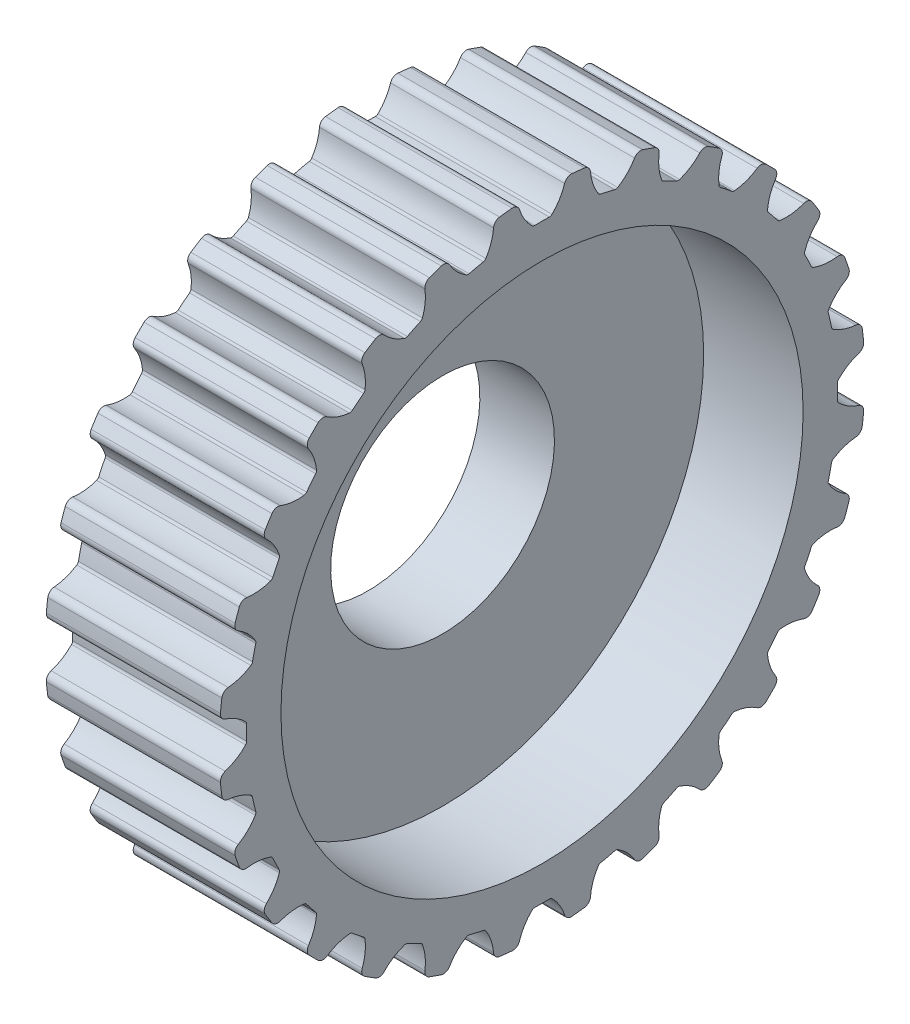
SolidWorks part; units mm, degrees
material "POM 乙缩醛共聚物"
ref_plane "前视基准面" through (0, 0, 0) normal (0, 0, 1) x (1, 0, 0)
ref_plane "上视基准面" through (0, 0, 0) normal (0, 1, 0) x (1, 0, 0)
ref_plane "右视基准面" through (0, 0, 0) normal (1, 0, 0) x (0, 0, -1)
ref_plane "基准面1" through (0, 0, 0) normal (0, 0, 1) x (1, 0, 0)
sketch "草图1" plane through (0, 0, 0) normal (0, 0, 1) x (1, 0, 0)
  line L0 (0, 0) -> (0, 10)
  line L1 (0, 10) -> (1, 10)
  line L2 (1, 10) -> (1, 12.8583)
  line L3 (1, 12.8583) -> (0.4955, 14.7412)
  line L4 (0.4955, 14.7412) -> (1.4614, 15)
  line L5 (1.4614, 15) -> (2, 12.99)
  line L6 (2, 12.99) -> (9, 12.99)
  line L7 (9, 12.99) -> (9.5386, 15)
  line L8 (9.5386, 15) -> (10.5045, 14.7412)
  line L9 (10.5045, 14.7412) -> (10, 12.8583)
  line L10 (10, 12.8583) -> (10, 10)
  line L11 (10, 10) -> (11, 10)
  line L12 (11, 10) -> (11, 0)
  line L13 (11, 0) -> (0, 0)
  line L14 (11, 0) -> (0, 0) construction
revolve "旋转1" add sketch "草图1" angle 360 about L14 reverse direction yes
ref_plane "基准面2" through (0, 0, 0) normal (0, 0, 1) x (1, 0, 0)
hole_wizard "孔1" positions "草图3" profile "草图2" legacy
sketch "草图3" plane through (11, 0, 0) normal (1, 0, 0) x (0, 0, -1)
  point P0 (0, 0)
sketch "草图2" plane through (11, 0, 0) normal (0, 1, 0) x (0, 0, -1)
  line L0 (0, 0) -> (0, 11)
  line L1 (0, 11) -> (4.5, 11)
  line L2 (4.5, 11) -> (4.5, 0)
  line L3 (4.5, 0) -> (0, 0)
  line L4 (0, 110) -> (0, -10) construction
  dimension "直径" = 9
  dimension "深度" = 11
ref_plane "基准面3" through (2, 0, 0) normal (1, 0, 0) x (0, 0, -1)
sketch "草图4" plane through (2, 0, 0) normal (1, 0, 0) x (0, 0, -1)
  circle A0 centre (0, 0) radius 17.99
  arc A1 (-12.9343, 1.2013) -> (-12.7398, 0.9084) centre (-12.6555, 1.1754) ccw
  arc A2 (-12.7398, 0.9084) -> (-11.9188, 0.4022) centre (-13.3344, -0.975) cw
  arc A3 (-11.9188, 0.4022) -> (-11.8764, 0.2939) centre (-12.0263, 0.2976) cw
  arc A4 (-11.8764, 0.2939) -> (-11.8764, -0.2939) centre (0, 0) ccw
  arc A5 (-11.8764, -0.2939) -> (-11.9188, -0.4022) centre (-12.0263, -0.2976) cw
  arc A6 (-11.9188, -0.4022) -> (-12.7398, -0.9084) centre (-13.3344, 0.975) cw
  arc A7 (-12.7398, -0.9084) -> (-12.9343, -1.2013) centre (-12.6555, -1.1754) ccw
  arc A8 (-12.9343, -1.2013) -> (-12.8774, -1.707) centre (0, 0) ccw
  arc A9 (-12.8774, -1.707) -> (-12.6225, -1.9493) centre (-12.5998, -1.6702) ccw
  arc A10 (-12.6225, -1.9493) -> (-11.7095, -2.2601) centre (-12.7831, -3.9177) cw
  arc A11 (-11.7095, -2.2601) -> (-11.644, -2.3562) centre (-11.791, -2.386) cw
  arc A12 (-11.644, -2.3562) -> (-11.5132, -2.9293) centre (0, 0) ccw
  arc A13 (-11.5132, -2.9293) -> (-11.5305, -3.0443) centre (-11.6586, -2.9663) cw
  arc A14 (-11.5305, -3.0443) -> (-12.2183, -3.7205) centre (-13.217, -2.0166) cw
  arc A15 (-12.2183, -3.7205) -> (-12.3427, -4.0493) centre (-12.0767, -3.962) ccw
  arc A16 (-12.3427, -4.0493) -> (-12.1746, -4.5297) centre (0, 0) ccw
  arc A17 (-12.1746, -4.5297) -> (-11.8723, -4.7092) centre (-11.9122, -4.432) ccw
  arc A18 (-11.8723, -4.7092) -> (-10.913, -4.809) centre (-11.5908, -6.664) cw
  arc A19 (-10.913, -4.809) -> (-10.8278, -4.8882) centre (-10.9645, -4.9499) cw
  arc A20 (-10.8278, -4.8882) -> (-10.5727, -5.4178) centre (0, 0) ccw
  arc A21 (-10.5727, -5.4178) -> (-10.564, -5.5338) centre (-10.7062, -5.4862) cw
  arc A22 (-10.564, -5.5338) -> (-11.0841, -6.346) centre (-12.4369, -4.9071) cw
  arc A23 (-11.0841, -6.346) -> (-11.1322, -6.6943) centre (-10.8923, -6.55) ccw
  arc A24 (-11.1322, -6.6943) -> (-10.8615, -7.1252) centre (0, 0) ccw
  arc A25 (-10.8615, -7.1252) -> (-10.5268, -7.233) centre (-10.6273, -6.9716) ccw
  arc A26 (-10.5268, -7.233) -> (-9.5693, -7.1168) centre (-9.8174, -9.0761) cw
  arc A27 (-9.5693, -7.1168) -> (-9.4686, -7.175) centre (-9.5881, -7.2656) cw
  arc A28 (-9.4686, -7.175) -> (-9.1021, -7.6346) centre (0, 0) ccw
  arc A29 (-9.1021, -7.6346) -> (-9.0677, -7.7457) centre (-9.217, -7.731) cw
  arc A30 (-9.0677, -7.7457) -> (-9.394, -8.6534) centre (-11.0332, -7.5516) cw
  arc A31 (-9.394, -8.6534) -> (-9.3635, -9.0036) centre (-9.1617, -8.8096) ccw
  arc A32 (-9.3635, -9.0036) -> (-9.0036, -9.3635) centre (0, 0) ccw
  arc A33 (-9.0036, -9.3635) -> (-8.6534, -9.394) centre (-8.8096, -9.1617) ccw
  arc A34 (-8.6534, -9.394) -> (-7.7457, -9.0677) centre (-7.5516, -11.0332) cw
  arc A35 (-7.7457, -9.0677) -> (-7.6346, -9.1021) centre (-7.731, -9.217) cw
  arc A36 (-7.6346, -9.1021) -> (-7.175, -9.4686) centre (0, 0) ccw
  arc A37 (-7.175, -9.4686) -> (-7.1168, -9.5693) centre (-7.2656, -9.5881) cw
  arc A38 (-7.1168, -9.5693) -> (-7.233, -10.5268) centre (-9.0761, -9.8174) cw
  arc A39 (-7.233, -10.5268) -> (-7.1252, -10.8615) centre (-6.9716, -10.6273) ccw
  arc A40 (-7.1252, -10.8615) -> (-6.6943, -11.1322) centre (0, 0) ccw
  arc A41 (-6.6943, -11.1322) -> (-6.346, -11.0841) centre (-6.55, -10.8923) ccw
  arc A42 (-6.346, -11.0841) -> (-5.5338, -10.564) centre (-4.9071, -12.4369) cw
  arc A43 (-5.5338, -10.564) -> (-5.4178, -10.5727) centre (-5.4862, -10.7062) cw
  arc A44 (-5.4178, -10.5727) -> (-4.8882, -10.8278) centre (0, 0) ccw
  arc A45 (-4.8882, -10.8278) -> (-4.809, -10.913) centre (-4.9499, -10.9645) cw
  arc A46 (-4.809, -10.913) -> (-4.7092, -11.8723) centre (-6.664, -11.5908) cw
  arc A47 (-4.7092, -11.8723) -> (-4.5297, -12.1746) centre (-4.432, -11.9122) ccw
  arc A48 (-4.5297, -12.1746) -> (-4.0493, -12.3427) centre (0, 0) ccw
  arc A49 (-4.0493, -12.3427) -> (-3.7205, -12.2183) centre (-3.962, -12.0767) ccw
  arc A50 (-3.7205, -12.2183) -> (-3.0443, -11.5305) centre (-2.0166, -13.217) cw
  arc A51 (-3.0443, -11.5305) -> (-2.9293, -11.5132) centre (-2.9663, -11.6586) cw
  arc A52 (-2.9293, -11.5132) -> (-2.3562, -11.644) centre (0, 0) ccw
  arc A53 (-2.3562, -11.644) -> (-2.2601, -11.7095) centre (-2.386, -11.791) cw
  arc A54 (-2.2601, -11.7095) -> (-1.9493, -12.6225) centre (-3.9177, -12.7831) cw
  arc A55 (-1.9493, -12.6225) -> (-1.707, -12.8774) centre (-1.6702, -12.5998) ccw
  arc A56 (-1.707, -12.8774) -> (-1.2013, -12.9343) centre (0, 0) ccw
  arc A57 (-1.2013, -12.9343) -> (-0.9084, -12.7398) centre (-1.1754, -12.6555) ccw
  arc A58 (-0.9084, -12.7398) -> (-0.4022, -11.9188) centre (0.975, -13.3344) cw
  arc A59 (-0.4022, -11.9188) -> (-0.2939, -11.8764) centre (-0.2976, -12.0263) cw
  arc A60 (-0.2939, -11.8764) -> (0.2939, -11.8764) centre (0, 0) ccw
  arc A61 (0.2939, -11.8764) -> (0.4022, -11.9188) centre (0.2976, -12.0263) cw
  arc A62 (0.4022, -11.9188) -> (0.9084, -12.7398) centre (-0.975, -13.3344) cw
  arc A63 (0.9084, -12.7398) -> (1.2013, -12.9343) centre (1.1754, -12.6555) ccw
  arc A64 (1.2013, -12.9343) -> (1.707, -12.8774) centre (0, 0) ccw
  arc A65 (1.707, -12.8774) -> (1.9493, -12.6225) centre (1.6702, -12.5998) ccw
  arc A66 (1.9493, -12.6225) -> (2.2601, -11.7095) centre (3.9177, -12.7831) cw
  arc A67 (2.2601, -11.7095) -> (2.3562, -11.644) centre (2.386, -11.791) cw
  arc A68 (2.3562, -11.644) -> (2.9293, -11.5132) centre (0, 0) ccw
  arc A69 (2.9293, -11.5132) -> (3.0443, -11.5305) centre (2.9663, -11.6586) cw
  arc A70 (3.0443, -11.5305) -> (3.7205, -12.2183) centre (2.0166, -13.217) cw
  arc A71 (3.7205, -12.2183) -> (4.0493, -12.3427) centre (3.962, -12.0767) ccw
  arc A72 (4.0493, -12.3427) -> (4.5297, -12.1746) centre (0, 0) ccw
  arc A73 (4.5297, -12.1746) -> (4.7092, -11.8723) centre (4.432, -11.9122) ccw
  arc A74 (4.7092, -11.8723) -> (4.809, -10.913) centre (6.664, -11.5908) cw
  arc A75 (4.809, -10.913) -> (4.8882, -10.8278) centre (4.9499, -10.9645) cw
  arc A76 (4.8882, -10.8278) -> (5.4178, -10.5727) centre (0, 0) ccw
  arc A77 (5.4178, -10.5727) -> (5.5338, -10.564) centre (5.4862, -10.7062) cw
  arc A78 (5.5338, -10.564) -> (6.346, -11.0841) centre (4.9071, -12.4369) cw
  arc A79 (6.346, -11.0841) -> (6.6943, -11.1322) centre (6.55, -10.8923) ccw
  arc A80 (6.6943, -11.1322) -> (7.1252, -10.8615) centre (0, 0) ccw
  arc A81 (7.1252, -10.8615) -> (7.233, -10.5268) centre (6.9716, -10.6273) ccw
  arc A82 (7.233, -10.5268) -> (7.1168, -9.5693) centre (9.0761, -9.8174) cw
  arc A83 (7.1168, -9.5693) -> (7.175, -9.4686) centre (7.2656, -9.5881) cw
  arc A84 (7.175, -9.4686) -> (7.6346, -9.1021) centre (0, 0) ccw
  arc A85 (7.6346, -9.1021) -> (7.7457, -9.0677) centre (7.731, -9.217) cw
  arc A86 (7.7457, -9.0677) -> (8.6534, -9.394) centre (7.5516, -11.0332) cw
  arc A87 (8.6534, -9.394) -> (9.0036, -9.3635) centre (8.8096, -9.1617) ccw
  arc A88 (9.0036, -9.3635) -> (9.3635, -9.0036) centre (0, 0) ccw
  arc A89 (9.3635, -9.0036) -> (9.394, -8.6534) centre (9.1617, -8.8096) ccw
  arc A90 (9.394, -8.6534) -> (9.0677, -7.7457) centre (11.0332, -7.5516) cw
  arc A91 (9.0677, -7.7457) -> (9.1021, -7.6346) centre (9.217, -7.731) cw
  arc A92 (9.1021, -7.6346) -> (9.4686, -7.175) centre (0, 0) ccw
  arc A93 (9.4686, -7.175) -> (9.5693, -7.1168) centre (9.5881, -7.2656) cw
  arc A94 (9.5693, -7.1168) -> (10.5268, -7.233) centre (9.8174, -9.0761) cw
  arc A95 (10.5268, -7.233) -> (10.8615, -7.1252) centre (10.6273, -6.9716) ccw
  arc A96 (10.8615, -7.1252) -> (11.1322, -6.6943) centre (0, 0) ccw
  arc A97 (11.1322, -6.6943) -> (11.0841, -6.346) centre (10.8923, -6.55) ccw
  arc A98 (11.0841, -6.346) -> (10.564, -5.5338) centre (12.4369, -4.9071) cw
  arc A99 (10.564, -5.5338) -> (10.5727, -5.4178) centre (10.7062, -5.4862) cw
  arc A100 (10.5727, -5.4178) -> (10.8278, -4.8882) centre (0, 0) ccw
  arc A101 (10.8278, -4.8882) -> (10.913, -4.809) centre (10.9645, -4.9499) cw
  arc A102 (10.913, -4.809) -> (11.8723, -4.7092) centre (11.5908, -6.664) cw
  arc A103 (11.8723, -4.7092) -> (12.1746, -4.5297) centre (11.9122, -4.432) ccw
  arc A104 (12.1746, -4.5297) -> (12.3427, -4.0493) centre (0, 0) ccw
  arc A105 (12.3427, -4.0493) -> (12.2183, -3.7205) centre (12.0767, -3.962) ccw
  arc A106 (12.2183, -3.7205) -> (11.5305, -3.0443) centre (13.217, -2.0166) cw
  arc A107 (11.5305, -3.0443) -> (11.5132, -2.9293) centre (11.6586, -2.9663) cw
  arc A108 (11.5132, -2.9293) -> (11.644, -2.3562) centre (0, 0) ccw
  arc A109 (11.644, -2.3562) -> (11.7095, -2.2601) centre (11.791, -2.386) cw
  arc A110 (11.7095, -2.2601) -> (12.6225, -1.9493) centre (12.7831, -3.9177) cw
  arc A111 (12.6225, -1.9493) -> (12.8774, -1.707) centre (12.5998, -1.6702) ccw
  arc A112 (12.8774, -1.707) -> (12.9343, -1.2013) centre (0, 0) ccw
  arc A113 (12.9343, -1.2013) -> (12.7398, -0.9084) centre (12.6555, -1.1754) ccw
  arc A114 (12.7398, -0.9084) -> (11.9188, -0.4022) centre (13.3344, 0.975) cw
  arc A115 (11.9188, -0.4022) -> (11.8764, -0.2939) centre (12.0263, -0.2976) cw
  arc A116 (11.8764, -0.2939) -> (11.8764, 0.2939) centre (0, 0) ccw
  arc A117 (11.8764, 0.2939) -> (11.9188, 0.4022) centre (12.0263, 0.2976) cw
  arc A118 (11.9188, 0.4022) -> (12.7398, 0.9084) centre (13.3344, -0.975) cw
  arc A119 (12.7398, 0.9084) -> (12.9343, 1.2013) centre (12.6555, 1.1754) ccw
  arc A120 (12.9343, 1.2013) -> (12.8774, 1.707) centre (0, 0) ccw
  arc A121 (12.8774, 1.707) -> (12.6225, 1.9493) centre (12.5998, 1.6702) ccw
  arc A122 (12.6225, 1.9493) -> (11.7095, 2.2601) centre (12.7831, 3.9177) cw
  arc A123 (11.7095, 2.2601) -> (11.644, 2.3562) centre (11.791, 2.386) cw
  arc A124 (11.644, 2.3562) -> (11.5132, 2.9293) centre (0, 0) ccw
  arc A125 (11.5132, 2.9293) -> (11.5305, 3.0443) centre (11.6586, 2.9663) cw
  arc A126 (11.5305, 3.0443) -> (12.2183, 3.7205) centre (13.217, 2.0166) cw
  arc A127 (12.2183, 3.7205) -> (12.3427, 4.0493) centre (12.0767, 3.962) ccw
  arc A128 (12.3427, 4.0493) -> (12.1746, 4.5297) centre (0, 0) ccw
  arc A129 (12.1746, 4.5297) -> (11.8723, 4.7092) centre (11.9122, 4.432) ccw
  arc A130 (11.8723, 4.7092) -> (10.913, 4.809) centre (11.5908, 6.664) cw
  arc A131 (10.913, 4.809) -> (10.8278, 4.8882) centre (10.9645, 4.9499) cw
  arc A132 (10.8278, 4.8882) -> (10.5727, 5.4178) centre (0, 0) ccw
  arc A133 (10.5727, 5.4178) -> (10.564, 5.5338) centre (10.7062, 5.4862) cw
  arc A134 (10.564, 5.5338) -> (11.0841, 6.346) centre (12.4369, 4.9071) cw
  arc A135 (11.0841, 6.346) -> (11.1322, 6.6943) centre (10.8923, 6.55) ccw
  arc A136 (11.1322, 6.6943) -> (10.8615, 7.1252) centre (0, 0) ccw
  arc A137 (10.8615, 7.1252) -> (10.5268, 7.233) centre (10.6273, 6.9716) ccw
  arc A138 (10.5268, 7.233) -> (9.5693, 7.1168) centre (9.8174, 9.0761) cw
  arc A139 (9.5693, 7.1168) -> (9.4686, 7.175) centre (9.5881, 7.2656) cw
  arc A140 (9.4686, 7.175) -> (9.1021, 7.6346) centre (0, 0) ccw
  arc A141 (9.1021, 7.6346) -> (9.0677, 7.7457) centre (9.217, 7.731) cw
  arc A142 (9.0677, 7.7457) -> (9.394, 8.6534) centre (11.0332, 7.5516) cw
  arc A143 (9.394, 8.6534) -> (9.3635, 9.0036) centre (9.1617, 8.8096) ccw
  arc A144 (9.3635, 9.0036) -> (9.0036, 9.3635) centre (0, 0) ccw
  arc A145 (9.0036, 9.3635) -> (8.6534, 9.394) centre (8.8096, 9.1617) ccw
  arc A146 (8.6534, 9.394) -> (7.7457, 9.0677) centre (7.5516, 11.0332) cw
  arc A147 (7.7457, 9.0677) -> (7.6346, 9.1021) centre (7.731, 9.217) cw
  arc A148 (7.6346, 9.1021) -> (7.175, 9.4686) centre (0, 0) ccw
  arc A149 (7.175, 9.4686) -> (7.1168, 9.5693) centre (7.2656, 9.5881) cw
  arc A150 (7.1168, 9.5693) -> (7.233, 10.5268) centre (9.0761, 9.8174) cw
  arc A151 (7.233, 10.5268) -> (7.1252, 10.8615) centre (6.9716, 10.6273) ccw
  arc A152 (7.1252, 10.8615) -> (6.6943, 11.1322) centre (0, 0) ccw
  arc A153 (6.6943, 11.1322) -> (6.346, 11.0841) centre (6.55, 10.8923) ccw
  arc A154 (6.346, 11.0841) -> (5.5338, 10.564) centre (4.9071, 12.4369) cw
  arc A155 (5.5338, 10.564) -> (5.4178, 10.5727) centre (5.4862, 10.7062) cw
  arc A156 (5.4178, 10.5727) -> (4.8882, 10.8278) centre (0, 0) ccw
  arc A157 (4.8882, 10.8278) -> (4.809, 10.913) centre (4.9499, 10.9645) cw
  arc A158 (4.809, 10.913) -> (4.7092, 11.8723) centre (6.664, 11.5908) cw
  arc A159 (4.7092, 11.8723) -> (4.5297, 12.1746) centre (4.432, 11.9122) ccw
  arc A160 (4.5297, 12.1746) -> (4.0493, 12.3427) centre (0, 0) ccw
  arc A161 (4.0493, 12.3427) -> (3.7205, 12.2183) centre (3.962, 12.0767) ccw
  arc A162 (3.7205, 12.2183) -> (3.0443, 11.5305) centre (2.0166, 13.217) cw
  arc A163 (3.0443, 11.5305) -> (2.9293, 11.5132) centre (2.9663, 11.6586) cw
  arc A164 (2.9293, 11.5132) -> (2.3562, 11.644) centre (0, 0) ccw
  arc A165 (2.3562, 11.644) -> (2.2601, 11.7095) centre (2.386, 11.791) cw
  arc A166 (2.2601, 11.7095) -> (1.9493, 12.6225) centre (3.9177, 12.7831) cw
  arc A167 (1.9493, 12.6225) -> (1.707, 12.8774) centre (1.6702, 12.5998) ccw
  arc A168 (1.707, 12.8774) -> (1.2013, 12.9343) centre (0, 0) ccw
  arc A169 (1.2013, 12.9343) -> (0.9084, 12.7398) centre (1.1754, 12.6555) ccw
  arc A170 (0.9084, 12.7398) -> (0.4022, 11.9188) centre (-0.975, 13.3344) cw
  arc A171 (0.4022, 11.9188) -> (0.2939, 11.8764) centre (0.2976, 12.0263) cw
  arc A172 (0.2939, 11.8764) -> (-0.2939, 11.8764) centre (0, 0) ccw
  arc A173 (-0.2939, 11.8764) -> (-0.4022, 11.9188) centre (-0.2976, 12.0263) cw
  arc A174 (-0.4022, 11.9188) -> (-0.9084, 12.7398) centre (0.975, 13.3344) cw
  arc A175 (-0.9084, 12.7398) -> (-1.2013, 12.9343) centre (-1.1754, 12.6555) ccw
  arc A176 (-1.2013, 12.9343) -> (-1.707, 12.8774) centre (0, 0) ccw
  arc A177 (-1.707, 12.8774) -> (-1.9493, 12.6225) centre (-1.6702, 12.5998) ccw
  arc A178 (-1.9493, 12.6225) -> (-2.2601, 11.7095) centre (-3.9177, 12.7831) cw
  arc A179 (-2.2601, 11.7095) -> (-2.3562, 11.644) centre (-2.386, 11.791) cw
  arc A180 (-2.3562, 11.644) -> (-2.9293, 11.5132) centre (0, 0) ccw
  arc A181 (-2.9293, 11.5132) -> (-3.0443, 11.5305) centre (-2.9663, 11.6586) cw
  arc A182 (-3.0443, 11.5305) -> (-3.7205, 12.2183) centre (-2.0166, 13.217) cw
  arc A183 (-3.7205, 12.2183) -> (-4.0493, 12.3427) centre (-3.962, 12.0767) ccw
  arc A184 (-4.0493, 12.3427) -> (-4.5297, 12.1746) centre (0, 0) ccw
  arc A185 (-4.5297, 12.1746) -> (-4.7092, 11.8723) centre (-4.432, 11.9122) ccw
  arc A186 (-4.7092, 11.8723) -> (-4.809, 10.913) centre (-6.664, 11.5908) cw
  arc A187 (-4.809, 10.913) -> (-4.8882, 10.8278) centre (-4.9499, 10.9645) cw
  arc A188 (-4.8882, 10.8278) -> (-5.4178, 10.5727) centre (0, 0) ccw
  arc A189 (-5.4178, 10.5727) -> (-5.5338, 10.564) centre (-5.4862, 10.7062) cw
  arc A190 (-5.5338, 10.564) -> (-6.346, 11.0841) centre (-4.9071, 12.4369) cw
  arc A191 (-6.346, 11.0841) -> (-6.6943, 11.1322) centre (-6.55, 10.8923) ccw
  arc A192 (-6.6943, 11.1322) -> (-7.1252, 10.8615) centre (0, 0) ccw
  arc A193 (-7.1252, 10.8615) -> (-7.233, 10.5268) centre (-6.9716, 10.6273) ccw
  arc A194 (-7.233, 10.5268) -> (-7.1168, 9.5693) centre (-9.0761, 9.8174) cw
  arc A195 (-7.1168, 9.5693) -> (-7.175, 9.4686) centre (-7.2656, 9.5881) cw
  arc A196 (-7.175, 9.4686) -> (-7.6346, 9.1021) centre (0, 0) ccw
  arc A197 (-7.6346, 9.1021) -> (-7.7457, 9.0677) centre (-7.731, 9.217) cw
  arc A198 (-7.7457, 9.0677) -> (-8.6534, 9.394) centre (-7.5516, 11.0332) cw
  arc A199 (-8.6534, 9.394) -> (-9.0036, 9.3635) centre (-8.8096, 9.1617) ccw
  arc A200 (-9.0036, 9.3635) -> (-9.3635, 9.0036) centre (0, 0) ccw
  arc A201 (-9.3635, 9.0036) -> (-9.394, 8.6534) centre (-9.1617, 8.8096) ccw
  arc A202 (-9.394, 8.6534) -> (-9.0677, 7.7457) centre (-11.0332, 7.5516) cw
  arc A203 (-9.0677, 7.7457) -> (-9.1021, 7.6346) centre (-9.217, 7.731) cw
  arc A204 (-9.1021, 7.6346) -> (-9.4686, 7.175) centre (0, 0) ccw
  arc A205 (-9.4686, 7.175) -> (-9.5693, 7.1168) centre (-9.5881, 7.2656) cw
  arc A206 (-9.5693, 7.1168) -> (-10.5268, 7.233) centre (-9.8174, 9.0761) cw
  arc A207 (-10.5268, 7.233) -> (-10.8615, 7.1252) centre (-10.6273, 6.9716) ccw
  arc A208 (-10.8615, 7.1252) -> (-11.1322, 6.6943) centre (0, 0) ccw
  arc A209 (-11.1322, 6.6943) -> (-11.0841, 6.346) centre (-10.8923, 6.55) ccw
  arc A210 (-11.0841, 6.346) -> (-10.564, 5.5338) centre (-12.4369, 4.9071) cw
  arc A211 (-10.564, 5.5338) -> (-10.5727, 5.4178) centre (-10.7062, 5.4862) cw
  arc A212 (-10.5727, 5.4178) -> (-10.8278, 4.8882) centre (0, 0) ccw
  arc A213 (-10.8278, 4.8882) -> (-10.913, 4.809) centre (-10.9645, 4.9499) cw
  arc A214 (-10.913, 4.809) -> (-11.8723, 4.7092) centre (-11.5908, 6.664) cw
  arc A215 (-11.8723, 4.7092) -> (-12.1746, 4.5297) centre (-11.9122, 4.432) ccw
  arc A216 (-12.1746, 4.5297) -> (-12.3427, 4.0493) centre (0, 0) ccw
  arc A217 (-12.3427, 4.0493) -> (-12.2183, 3.7205) centre (-12.0767, 3.962) ccw
  arc A218 (-12.2183, 3.7205) -> (-11.5305, 3.0443) centre (-13.217, 2.0166) cw
  arc A219 (-11.5305, 3.0443) -> (-11.5132, 2.9293) centre (-11.6586, 2.9663) cw
  arc A220 (-11.5132, 2.9293) -> (-11.644, 2.3562) centre (0, 0) ccw
  arc A221 (-11.644, 2.3562) -> (-11.7095, 2.2601) centre (-11.791, 2.386) cw
  arc A222 (-11.7095, 2.2601) -> (-12.6225, 1.9493) centre (-12.7831, 3.9177) cw
  arc A223 (-12.6225, 1.9493) -> (-12.8774, 1.707) centre (-12.5998, 1.6702) ccw
  arc A224 (-12.8774, 1.707) -> (-12.9343, 1.2013) centre (0, 0) ccw
extrude "切除-拉伸1" cut sketch "草图4" along normal blind 7
ref_plane "基准面4" through (0, 0, 0) normal (0, 0, 1) x (1, 0, 0)
ref_plane "基准面5" through (5.5, 0, 0) normal (1, 0, 0) x (0, 0, -1)
ref_plane "to_belt XY" through (5.5, 0, 0) normal (-1, 0, 0) x (0, 0, 1)
ref_plane "to_belt XZ" through (0, 0, 0) normal (0, 1, 0) x (1, 0, 0)
ref_plane "to_belt YZ" through (0, 0, 0) normal (0, 0, -1) x (-1, 0, 0)
ref_axis "to_belt X" through (5.5, 0, 80.9) along (0, 0, -1)
ref_axis "to_belt Y" through (5.5, 50, 0) along (0, -1, 0)
ref_axis "to_belt Z" through (-80.9, 0, 0) along (1, 0, 0)
sketch3d "to_belt"
  point P0 (5.5, 0, 0)
sketch "草图5" plane through (0, 0, 0) normal (0, 0, 1) x (1, 0, 0)
  line L1 (-9.0658, 15.8819) -> (2, 15.8819)
  line L2 (-9.0658, 15.8819) -> (-9.0658, -15.6579)
  line L3 (-9.0658, -15.6579) -> (2, -15.6579)
  line L4 (2, 15.8819) -> (2, -15.6579)
  line L5 (9, 15.8819) -> (22.3954, 15.8819)
  line L6 (9, 15.8819) -> (9, -15.6579)
  line L7 (9, -15.6579) -> (22.3954, -15.6579)
  line L8 (22.3954, 15.8819) -> (22.3954, -15.6579)
extrude "切除-拉伸2" cut sketch "草图5" against normal through all both and the other way through all
sketch "草图6" plane through (9, 0, 0) normal (1, 0, 0) x (0, 0, -1)
  circle A0 centre (0, 0) radius 10.5
  dimension "D1" = 21
extrude "切除-拉伸3" cut sketch "草图6" against normal offset from surface (4 mm away) 3 up to face at (2, 0, 0)
